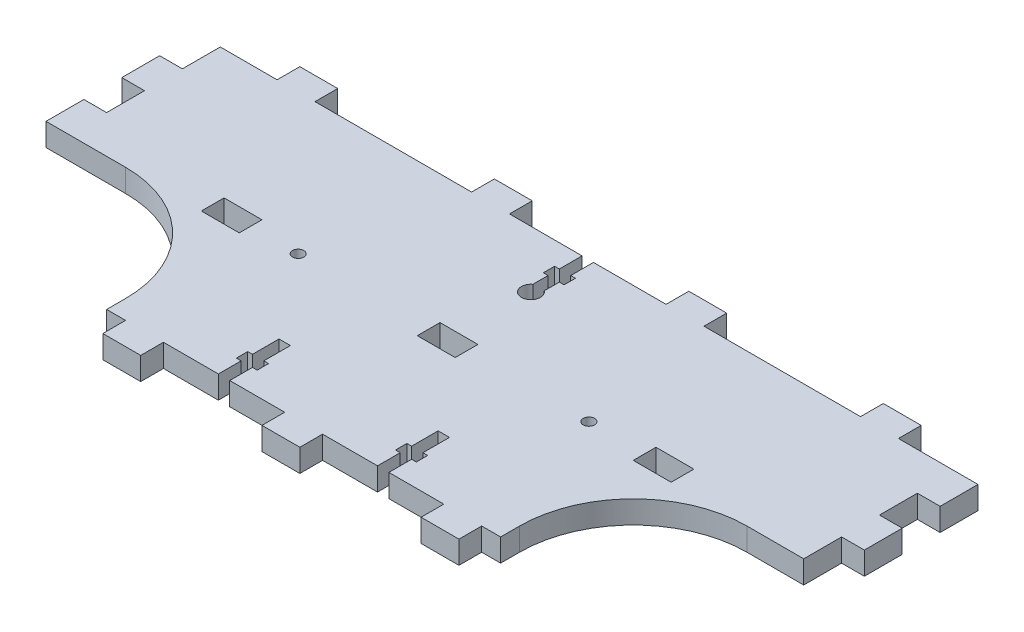
SolidWorks part; units mm, degrees
material "Pine"
ref_plane "Front Plane" through (0, 0, 0) normal (0, 0, 1) x (1, 0, 0)
ref_plane "Top Plane" through (0, 0, 0) normal (0, 1, 0) x (1, 0, 0)
ref_plane "Right Plane" through (0, 0, 0) normal (1, 0, 0) x (0, 0, -1)
sketch "Sketch1" plane through (0, 0, 0) normal (0, 1, 0) x (1, 0, 0)
  line L0 (-134, -3) -> (-102, -3) construction
  line L1 (0, 0) -> (-194, 0)
  line L2 (0, 0) -> (0, 75)
  line L3 (0, 75) -> (-194, 75)
  line L4 (-194, 0) -> (-194, 75)
  line L5 (-144, 0) -> (-134, 0)
  line L6 (-144, 0) -> (-144, -6)
  line L7 (-144, -6) -> (-134, -6)
  line L8 (-134, 0) -> (-134, -6)
  line L9 (-102, 0) -> (-92, 0)
  line L10 (-102, 0) -> (-102, -6)
  line L11 (-102, -6) -> (-92, -6)
  line L12 (-92, 0) -> (-92, -6)
  line L13 (-50, 0) -> (-60, 0)
  line L14 (-50, 0) -> (-50, -6)
  line L15 (-50, -6) -> (-60, -6)
  line L16 (-60, 0) -> (-60, -6)
  line L17 (-200, 45) -> (-194, 45)
  line L18 (-200, 45) -> (-200, 35)
  line L19 (-200, 35) -> (-194, 35)
  line L20 (-194, 45) -> (-194, 35)
  line L21 (-200, 65) -> (-194, 65)
  line L22 (-200, 65) -> (-200, 55)
  line L23 (-200, 55) -> (-194, 55)
  line L24 (-194, 65) -> (-194, 55)
  line L25 (-92, -3) -> (-60, -3) construction
  line L26 (-97, 75) -> (-97, 0) construction
  line L27 (0, 75) -> (6, 75)
  line L28 (0, 75) -> (0, 0)
  line L29 (0, 0) -> (6, 0)
  line L30 (6, 75) -> (6, 0)
  line L31 (6, 65) -> (0, 65)
  line L32 (6, 55) -> (0, 55)
  line L33 (6, 45) -> (0, 45)
  line L34 (6, 35) -> (0, 35)
  dimension "D1" = 194
  dimension "D2" = 75
  dimension "D3" = 6
  dimension "D4" = 10
  dimension "D5" = 50
  dimension "D6" = 50
  dimension "D7" = 10
  dimension "D8" = 6
  dimension "D9" = 35
  dimension "D10" = 10
  dimension "6" = 6
extrude "Boss-Extrude1" add sketch "Sketch1" along normal blind 6 contours L22 L23 L4 L21 | L4 L1 L2 L28 L3 | L8 L1 L6 L7 | L12 L1 L10 L11 | L1 L16 L15 L14 | L30 L34 L2 L29 | L33 L30 L32 L28 | L31 L30 L27 L28 | L18 L19 L20 L17 region at (-97, 0, -37.5) region at (3, 0, -17.5) region at (-55, 0, 3) region at (3, 0, -50) region at (-97, 0, 3) region at (3, 0, -70) region at (-139, 0, 3) region at (-197, 0, -60)
sketch "Sketch3" plane through (0, 6, 0) normal (0, 1, 0) x (1, 0, 0)
  line L0 (-97, -6) -> (-97, 75) construction
  line L1 (-194, 35) -> (-179, 35)
  line L2 (-194, 35) -> (-194, 0)
  line L3 (-194, 0) -> (-149, 0)
  line L4 (-149, 5) -> (-149, 0)
  line L5 (-102, -6) -> (-92, -6) construction
  line L6 (6, 75) -> (-194, 75) construction
  line L7 (0, 0) -> (-45, 0)
  line L8 (-45, 5) -> (-45, 0)
  line L9 (0, 35) -> (-15, 35)
  line L10 (0, 35) -> (0, 0)
  line L12 (0, 35) -> (6, 35)
  line L13 (0, 35) -> (0, 0)
  line L14 (0, 0) -> (6, 0)
  line L15 (6, 35) -> (6, 0)
  arc A0 (-149, 5) -> (-179, 35) centre (-179, 5) ccw
  arc A1 (-45, 5) -> (-15, 35) centre (-15, 5) cw
  line M13 (-194, 35) -> (-194, 0)
  line M14 (-194, 0) -> (-144, 0)
  line M26 (-50, 0) -> (6, 0)
  line M27 (6, 0) -> (6, 35)
  line M28 (6, 35) -> (0, 35)
  dimension "D1" = 30
  dimension "D2" = 45
extrude "Cut-Extrude2" cut sketch "Sketch3" against normal through all contours L4 A0 L1 M13 M14 | A1 L8 L10 L9 M26 | L10 M28 M26 M27 region at (-173.7082, 6, -15.9906) region at (-20.2918, 6, -15.9906) region at (3, 6, -17.5)
sketch "Sketch4" plane through (0, 6, 0) normal (0, 1, 0) x (1, 0, 0)
  line L0 (-102, 0) -> (-134, 0) construction
  line L1 (-119.5, 0) -> (-116.5, 0)
  line L2 (-119.5, 0) -> (-119.5, 16)
  line L3 (-119.5, 16) -> (-116.5, 16)
  line L4 (-116.5, 0) -> (-116.5, 16)
  line L5 (-60, 0) -> (-92, 0) construction
  line L6 (-77.5, 0) -> (-74.5, 0)
  line L7 (-77.5, 0) -> (-77.5, 16)
  line L8 (-77.5, 16) -> (-74.5, 16)
  line L9 (-74.5, 0) -> (-74.5, 16)
  line L11 (-120.75, 9) -> (-115.25, 9)
  line L12 (-120.75, 9) -> (-120.75, 6)
  line L13 (-120.75, 6) -> (-115.25, 6)
  line L14 (-115.25, 9) -> (-115.25, 6)
  line L15 (-78.75, 9) -> (-73.25, 9)
  line L16 (-78.75, 9) -> (-78.75, 6)
  line L17 (-78.75, 6) -> (-73.25, 6)
  line L18 (-73.25, 9) -> (-73.25, 6)
  point P20 (-118, 6)
  point P21 (-118, 16)
  point P22 (-76, 16)
  point P23 (-76, 6)
  point P24 (-118, 0)
  point P25 (-76, 0)
  dimension "D1" = 3
  dimension "D2" = 16
  dimension "D3" = 3
  dimension "D4" = 6
  dimension "D5" = 5.5
extrude "Cut-Extrude3" cut sketch "Sketch4" against normal through all contours L12 L13 L14 L11 | L4 L3 L2 L1 | L7 L8 L9 L6 | L17 L18 L15 L16
sketch "Sketch5" plane through (0, 0, 0) normal (0, -1, 0) x (1, 0, 0)
  line L0 (-159, -41) -> (-149, -41) construction
  line L1 (-149, -41) -> (-149, -35) construction
  line L2 (-149, -35) -> (-159, -35) construction
  line L3 (-159, -35) -> (-159, -41) construction
  line L4 (-102, -41) -> (-92, -41) construction
  line L5 (-92, -41) -> (-92, -35) construction
  line L6 (-92, -35) -> (-102, -35) construction
  line L7 (-102, -35) -> (-102, -41) construction
  line L8 (-45, -41) -> (-35, -41) construction
  line L9 (-35, -41) -> (-35, -35) construction
  line L10 (-35, -35) -> (-45, -35) construction
  line L11 (-45, -35) -> (-45, -41) construction
  line L12 (-159, -41) -> (-149, -41)
  line L13 (-149, -41) -> (-149, -35)
  line L14 (-149, -35) -> (-159, -35)
  line L15 (-159, -35) -> (-159, -41)
  line L16 (-102, -41) -> (-92, -41)
  line L17 (-92, -41) -> (-92, -35)
  line L18 (-92, -35) -> (-102, -35)
  line L19 (-102, -35) -> (-102, -41)
  line L20 (-45, -41) -> (-35, -41)
  line L21 (-35, -41) -> (-35, -35)
  line L22 (-35, -35) -> (-45, -35)
  line L23 (-45, -35) -> (-45, -41)
extrude "Cut-Extrude4" cut sketch "Sketch5" against normal through all
sketch "Sketch6" plane through (0, 0, 0) normal (0, -1, 0) x (1, 0, 0)
  line L4 (-134.9433, -41) -> (-137.9433, -41) construction
  line L5 (-137.9433, -41) -> (-137.9433, -35) construction
  line L6 (-137.9433, -35) -> (-134.9433, -35) construction
  line L7 (-134.9433, -35) -> (-134.9433, -41) construction
  line L12 (-134.9433, -41) -> (-137.9433, -41) construction
  line L13 (-137.9433, -41) -> (-137.9433, -35) construction
  line L14 (-137.9433, -35) -> (-134.9433, -35) construction
  line L15 (-134.9433, -35) -> (-134.9433, -41) construction
  line L20 (-61.2077, -41) -> (-58.2077, -41)
  line L21 (-58.2077, -41) -> (-58.2077, -35)
  line L22 (-58.2077, -35) -> (-61.2077, -35)
  line L23 (-61.2077, -35) -> (-61.2077, -41)
  line L24 (-61.2077, -41) -> (-58.2077, -41) construction
  line L25 (-58.2077, -41) -> (-58.2077, -35) construction
  line L26 (-58.2077, -35) -> (-61.2077, -35) construction
  line L27 (-61.2077, -35) -> (-61.2077, -41) construction
  circle A0 centre (-136.4433, -38) radius 1.5
  circle A1 centre (-59.7077, -38) radius 1.5
  point P3 (0, 0)
  point P10 (-59.7077, -35)
  point P14 (-136.4433, -41)
  point P15 (0, 0)
  point P16 (0, 0)
  point P17 (-61.2077, -38)
  dimension "D1" = 3
  dimension "D2" = 0
extrude "Cut-Extrude5" cut sketch "Sketch6" against normal through all
sketch "Sketch7" plane through (0, 6, 0) normal (0, 1, 0) x (1, 0, 0)
  line L0 (6, 75) -> (-194, 75) construction
  line L1 (-179, 75) -> (-169, 75)
  line L2 (-179, 75) -> (-179, 81)
  line L3 (-179, 81) -> (-169, 81)
  line L4 (-169, 75) -> (-169, 81)
  line L5 (-169, 78) -> (-127.6667, 78) construction
  line L6 (-127.6667, 75) -> (-117.6667, 75)
  line L7 (-127.6667, 75) -> (-127.6667, 81)
  line L8 (-127.6667, 81) -> (-117.6667, 81)
  line L9 (-117.6667, 75) -> (-117.6667, 81)
  line L10 (-76.3333, 75) -> (-66.3333, 75)
  line L11 (-76.3333, 75) -> (-76.3333, 81)
  line L12 (-76.3333, 81) -> (-66.3333, 81)
  line L13 (-66.3333, 75) -> (-66.3333, 81)
  line L14 (-25, 75) -> (-15, 75)
  line L15 (-25, 75) -> (-25, 81)
  line L16 (-25, 81) -> (-15, 81)
  line L17 (-15, 75) -> (-15, 81)
  line L18 (-117.6667, 78) -> (-76.3333, 78) construction
  line L19 (-66.3333, 78) -> (-25, 78) construction
  line L20 (-194, 65) -> (-194, 75) construction
  line L21 (0, 55) -> (0, 65) construction
  dimension "D1" = 6
  dimension "D2" = 10
  dimension "D3" = 15
  dimension "D4" = 15
extrude "Boss-Extrude2" add sketch "Sketch7" against normal blind 6
sketch "Sketch8" plane through (0, 0, 0) normal (0, -1, 0) x (1, 0, 0)
  line L0 (-76.3333, -75) -> (-117.6667, -75) construction
  circle A0 centre (-97, -60) radius 2.5
  point P5 (-97, -75)
  dimension "D1" = 5
  dimension "D2" = 15
extrude "Cut-Extrude6" cut sketch "Sketch8" against normal through all
sketch "Sketch9" plane through (0, 0, 0) normal (0, -1, 0) x (1, 0, 0)
  line L0 (-76.3333, -75) -> (-117.6667, -75) construction
  line L1 (-98.5, -75) -> (-95.5, -75)
  line L2 (-98.5, -75) -> (-98.5, -59)
  line L3 (-98.5, -59) -> (-95.5, -59)
  line L4 (-95.5, -75) -> (-95.5, -59)
  line L5 (-77.5, -16) -> (-74.5, -16) construction
  line L6 (-94.25, -69) -> (-99.75, -69)
  line L7 (-94.25, -69) -> (-94.25, -66)
  line L8 (-94.25, -66) -> (-99.75, -66)
  line L9 (-99.75, -69) -> (-99.75, -66)
  line L10 (-78.75, -9) -> (-78.75, -6) construction
  line L11 (-73.25, -9) -> (-73.25, -6) construction
  line L12 (-77.5, -16) -> (-74.5, -16) construction
  line L13 (-78.75, -9) -> (-78.75, -6) construction
  line L14 (-73.25, -9) -> (-73.25, -6) construction
  line L15 (-73.25, -9) -> (-78.75, -9) construction
  line L16 (-74.5, -16) -> (-74.5, 0) construction
  line L17 (-73.25, -6) -> (-73.25, 0) construction
  line L18 (-60, 0) -> (-74.5, 0) construction
  line L19 (-94.25, -69) -> (-94.25, -75) construction
  point P10 (-97, -59)
  point P11 (-97, -66)
  point P12 (-97, -75)
extrude "Cut-Extrude7" cut sketch "Sketch9" against normal blind 10 contours L8 L9 L6 L7 | L2 L3 L4 L1
